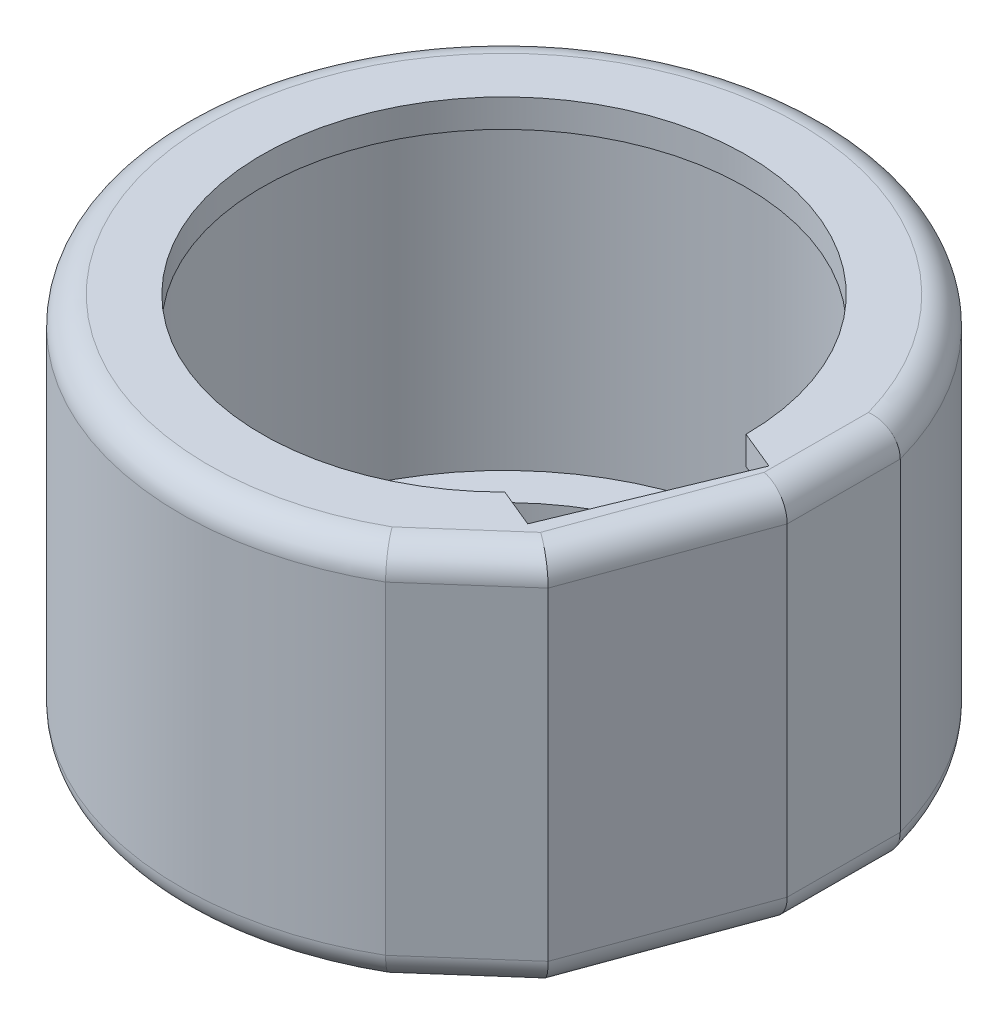
SolidWorks part; units mm, degrees
ref_plane "前视基准面" through (0, 0, 0) normal (0, 0, 1) x (1, 0, 0)
ref_plane "上视基准面" through (0, 0, 0) normal (0, 1, 0) x (1, 0, 0)
ref_plane "右视基准面" through (0, 0, 0) normal (1, 0, 0) x (0, 0, -1)
sketch "草图1" plane through (0, 0, 0) normal (0, 1, 0) x (1, 0, 0)
  line L0 (0, 0) -> (8.61, 0) construction
  line L1 (0, 0) -> (6.1027, -6.0736) construction
  line L6 (0, 0) -> (11.1178, 2.979) construction
  line L7 (0, 0) -> (5.755, -9.968) construction
  line L10 (8.61, 0) -> (11.1057, -1.0303) construction
  line L20 (11.1057, -1.0303) -> (8.831, -7.262)
  line L21 (11.1057, -1.0303) -> (11.1178, 2.979)
  line L22 (8.831, -7.262) -> (5.755, -9.968)
  line L23 (8.61, 0) -> (6.1027, -6.0736)
  arc A0 (8.61, 0) -> (6.1027, -6.0736) centre (0, 0) ccw
  arc A3 (11.1178, 2.979) -> (5.755, -9.968) centre (0, 0) ccw
  dimension "D1" = 2.7
  dimension "D2" = 11.51
  dimension "D3" = 8.61
extrude "凸台-拉伸1" add sketch "草图1" along normal blind 1
sketch "草图2" plane through (0, 0, 0) normal (0, -1, 0) x (-1, 0, 0)
  line L5 (0, 0) -> (-5.755, -9.968) construction
  line L7 (0, 0) -> (-11.1178, 2.979) construction
  line L9 (-7.3887, -6.7533) -> (-9.9999, -0.4493)
  line L17 (-11.1057, -1.0303) -> (-11.1178, 2.979)
  line L19 (-11.1057, -1.0303) -> (-8.831, -7.262)
  line L20 (-8.831, -7.262) -> (-5.755, -9.968)
  arc A0 (-5.755, -9.968) -> (-11.1178, 2.979) centre (0, 0) ccw
  arc A1 (-7.3887, -6.7533) -> (-9.9999, -0.4493) centre (0, 0) ccw
  dimension "D1" = 10.01
  dimension "D2" = 11.51
extrude "凸台-拉伸3" add sketch "草图2" along normal blind 11.5
sketch "草图5" plane through (0, -11.5, 0) normal (0, -1, 0) x (-1, 0, 0)
  line L4 (0, 0) -> (-5.755, -9.968) construction
  line L5 (0, 0) -> (-11.1178, 2.979) construction
  line L17 (-11.1178, 2.979) -> (-11.1057, -1.0303)
  line L19 (-8.831, -7.262) -> (-5.755, -9.968)
  line L21 (-8.61, 0) -> (-6.1027, -6.0736) construction
  line L22 (-8.61, 0) -> (-6.1027, -6.0736)
  line L23 (-11.1057, -1.0303) -> (-8.831, -7.262)
  arc A1 (-5.755, -9.968) -> (-11.1178, 2.979) centre (0, 0) ccw
  arc A2 (-6.1027, -6.0736) -> (-8.61, 0) centre (0, 0) ccw construction
  arc A3 (-6.1027, -6.0736) -> (-8.61, 0) centre (0, 0) ccw
extrude "凸台-拉伸4" add sketch "草图5" along normal blind 1
fillet "圆角1" radius 1 4 edges at (11.1118, -12.5, -0.9744) (-10.6339, -12.5, -4.4047) (7.293, -12.5, 8.615) (9.9683, -12.5, 4.1461) type face fillet first side face at (11.1118, -5.75, -0.9744) first side face at (9.9683, -5.75, 4.1461) first side face at (7.293, -5.75, 8.615) first side face at (-1.0987, -5.75, -0.4551) second side face at (4.4348, -12.5, 1.8455)
fillet "圆角2" radius 1 4 edges at (11.1118, 1, -0.9744) (-10.6339, 1, -4.4047) (7.293, 1, 8.615) (9.9683, 1, 4.1461) type face fillet first side face at (11.1118, -5.25, -0.9744) first side face at (9.9683, -5.25, 4.1461) first side face at (7.293, -5.25, 8.615) first side face at (-1.0987, -5.25, -0.4551) second side face at (-0.3011, 1, -0.1243)
sketch "草图7" plane through (7.3564, 0, 3.0368) normal (-0.9243, 0, -0.3816) x (-0.3816, 0, 0.9243)
  line L4 (-3.2854, 1) -> (-3.2854, 0) construction
  line L5 (-3.2854, 1) -> (-3.2854, 0)
  line L6 (-3.2854, 1) -> (3.2854, 1) construction
  line L7 (-3.2854, 1) -> (3.2854, 1)
  line L9 (-3.2854, 0) -> (3.2854, 0)
  line L10 (-3.2854, 0) -> (-3.2854, 1)
  line L11 (-3.2854, 1) -> (3.2854, 1)
  line L12 (3.2854, 0) -> (3.2854, 1)
extrude "切除-拉伸1" cut sketch "草图7" against normal blind 1.5 contours L9 L12 L7 L5
sketch3d "3DSketch1"
  spline S0 degree 1 poles (-10.7986, 1999.9934, 3.9838) (-10.7986, -2011.4808, 3.9838) knots -173.912465 -173.912465 174.91137 174.91137 only from (-10.7986, 0, 3.9838) to (-10.7986, -11.5, 3.9838) construction
  spline S1 degree 1 poles (-10.7986, 0, 3.9838) (-10.7986, -11.5, 3.9838) knots 0 0 1 1
sketch3d "3DSketch2"
  spline S0 degree 3 poles (5.755, -5.75, 9.968) (-5.7357, -5.75, 16.6021) (-15.7114, -5.75, 7.8537) (-10.6339, -5.75, -4.4047) (-5.5563, -5.75, -16.6631) (7.6837, -5.75, -15.7953) (11.1178, -5.75, -2.979) knots 0 0 0 0 0.5 0.5 0.5 1 1 1 1 weights 1 0.547626 0.547626 1 0.547626 0.547626 1 construction
  spline S1 degree 3 poles (5.755, -5.75, 9.968) (-5.7357, -5.75, 16.6021) (-15.7114, -5.75, 7.8537) (-10.6339, -5.75, -4.4047) (-5.5563, -5.75, -16.6631) (7.6837, -5.75, -15.7953) (11.1178, -5.75, -2.979) knots 0 0 0 0 0.5 0.5 0.5 1 1 1 1 weights 1 0.547626 0.547626 1 0.547626 0.547626 1
ref_plane "Plane1" through (-10.7986, 0, 3.9838) normal (-0.9382, 0, 0.3461) x (0.3461, 0, 0.9382)
sketch "Sketch2" plane through (-10.7986, 0, 3.9838) normal (-0.9382, 0, 0.3461) x (0.3461, 0, 0.9382)
  line L0 (0, 0) -> (0, -11.5) construction
  circle A0 centre (0, -5.75) radius 0.8
  point P0 (0, -5.75)
extrude "Cut-Extrude1" cut sketch "Sketch2" against normal blind 10
